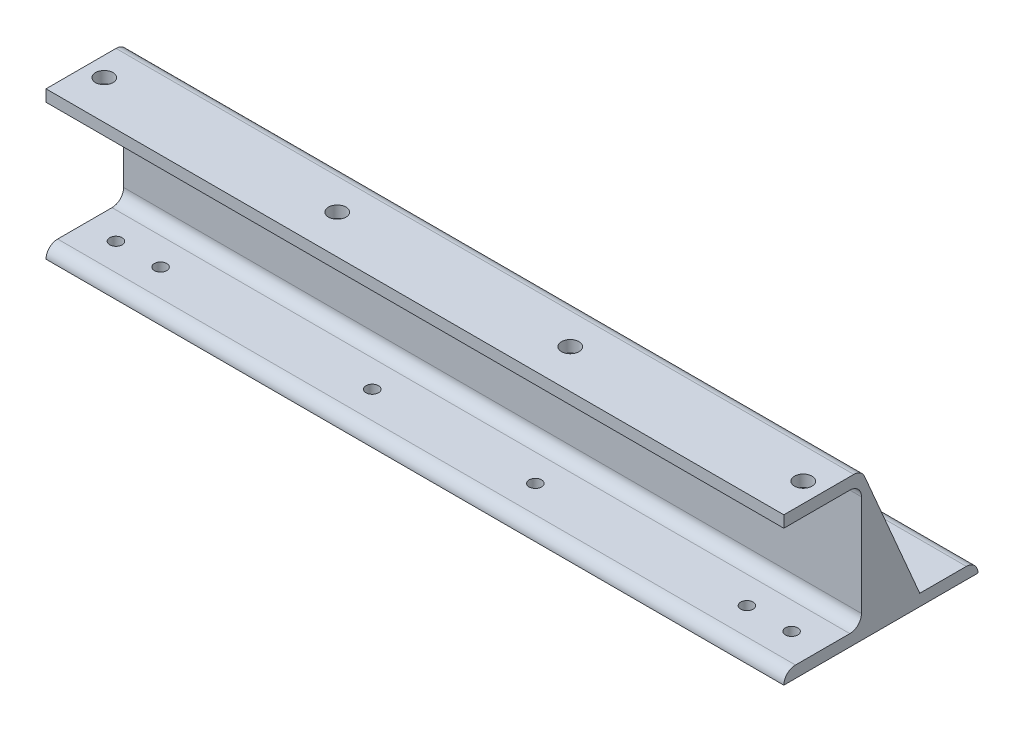
SolidWorks part; units mm, degrees
material "ABS"
ref_plane "Front Plane" through (0, 0, 0) normal (0, 0, 1) x (1, 0, 0)
ref_plane "Top Plane" through (0, 0, 0) normal (0, 1, 0) x (1, 0, 0)
ref_plane "Right Plane" through (0, 0, 0) normal (1, 0, 0) x (0, 0, -1)
sketch "Sketch1" plane through (0, 0, 0) normal (1, 0, 0) x (0, 0, -1)
  line L1 (0, 0) -> (-20, 0)
  line L2 (-20, 0) -> (-20, -3)
  line L7 (30, -35) -> (30, -38)
  line L8 (30, -38) -> (-20, -38)
  line L11 (15, -35) -> (30, -35)
  line L12 (-20, -3) -> (0, -3)
  line L13 (0, -3) -> (0, -35)
  line L14 (0, -35) -> (-20, -35)
  line L15 (-20, -35) -> (-20, -38)
  line L16 (0, 0) -> (15, -35)
  dimension "D1" = 20
  dimension "D2" = 15
  dimension "D3" = 3
  dimension "D4" = 50
  dimension "D5" = 38
  dimension "D6" = 3
extrude "Boss-Extrude1" add sketch "Sketch1" against normal blind 190
sketch "Sketch2" plane through (0, 0, 0) normal (0, 1, 0) x (1, 0, 0)
  line L1 (-190, 0) -> (-190, -20) construction
  line L3 (-190, 0) -> (0, 0) construction
  circle A0 centre (-185, -10) radius 2.25
  circle A2 centre (-125, -10) radius 2.25
  circle A3 centre (-65, -10) radius 2.25
  circle A4 centre (-5, -10) radius 2.25
  dimension "D1" = 4.5
  dimension "D2" = 10
  dimension "D3" = 4
  dimension "D4" = 5
  dimension "D5" = 60
extrude "Cut-Extrude1" cut sketch "Sketch2" against normal up to surface (3 mm away) up to face at (-95, -3, 10)
sketch "Sketch3" plane through (0, -38, 0) normal (0, -1, 0) x (1, 0, 0)
  line L0 (-190, 20) -> (0, 20) construction
  line L1 (-190, 20) -> (-190, -30) construction
  circle A0 centre (-116, 10) radius 1.6
  circle A1 centre (-74, 10) radius 1.6
  circle A2 centre (-182, 10) radius 1.6
  circle A3 centre (-170.5, 10) radius 1.6
  circle A4 centre (-19.5, 10) radius 1.6
  circle A5 centre (-8, 10) radius 1.6
  point P20 (-95, 20)
  dimension "D1" = 3.2
  dimension "D3" = 8
  dimension "D4" = 8
  dimension "D5" = 11.5
  dimension "D6" = 11.5
  dimension "D8" = 21
  dimension "D2" = 10
  dimension "D7" = 21
extrude "Cut-Extrude2" cut sketch "Sketch3" against normal up to surface (3 mm away) up to face at (-95, -35, 10)
sketch "Sketch4" plane through (0, -35, 0) normal (0, 1, 0) x (1, 0, 0)
  line L0 (-190, 30) -> (-190, 15) construction
  line L1 (-190, 30) -> (0, 30) construction
  circle A0 centre (-140, 21.5) radius 3.75
  circle A1 centre (-147.8, 21.5) radius 1.5
  dimension "D1" = 7.5
  dimension "D2" = 50
  dimension "D3" = 8.5
  dimension "D4" = 3
  dimension "D5" = 7.8
extrude "Cut-Extrude3" cut sketch "Sketch4" against normal up to surface (3 mm away) up to face at (-8, -38, 8.4)
fillet "Fillet1" radius 3 5 edges at (-95, -35, 0) (-95, -3, 0) (-95, -35, -30) (-95, -35, 20) (-95, 0, 0)
